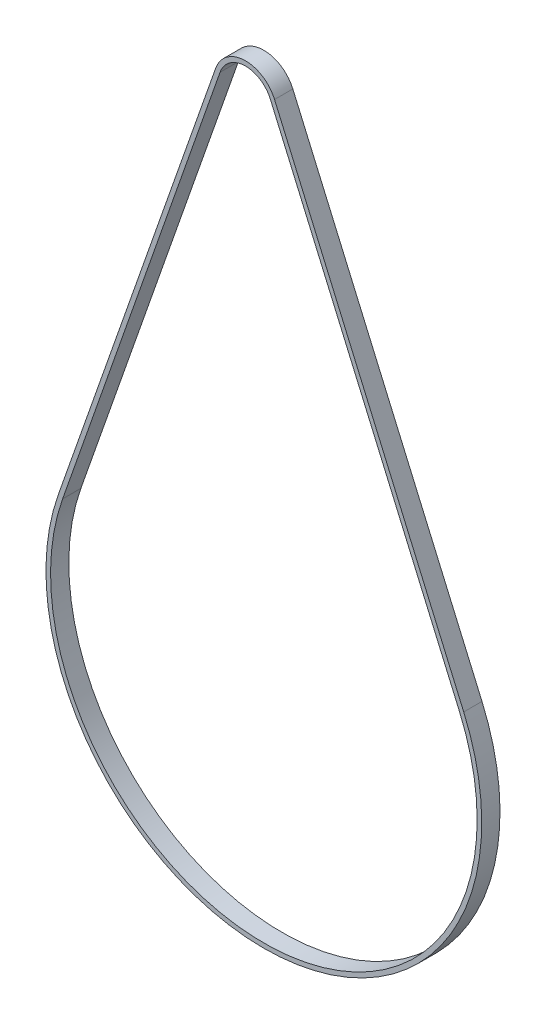
SolidWorks part; units mm, degrees
material "Silicon Rubber"
ref_plane "Front Plane" through (0, 0, 0) normal (0, 0, 1) x (1, 0, 0)
ref_plane "Top Plane" through (0, 0, 0) normal (0, 1, 0) x (1, 0, 0)
ref_plane "Right Plane" through (0, 0, 0) normal (1, 0, 0) x (0, 0, -1)
sketch "Sketch2" plane through (0, 0, 0) normal (0, 0, 1) x (1, 0, 0)
  line L0 (0, 0) -> (1, 0) construction
  line L1 (0, 0) -> (0, 1) construction
  line L6 (-82.5079, -139.1031) -> (-30.832, 7.9986)
  line L7 (-12.933, 8.6403) -> (49.1437, -134.3835)
  arc A1 (49.1437, -134.3835) -> (-82.5079, -139.1031) centre (-15.7568, -162.5523) cw
  arc A3 (-30.832, 7.9986) -> (-12.933, 8.6403) centre (-21.7567, 4.8105) cw
extrude "Extrude-Thin1" add sketch "Sketch2" along normal blind 6 thin thin type mid plane wall 1.5
